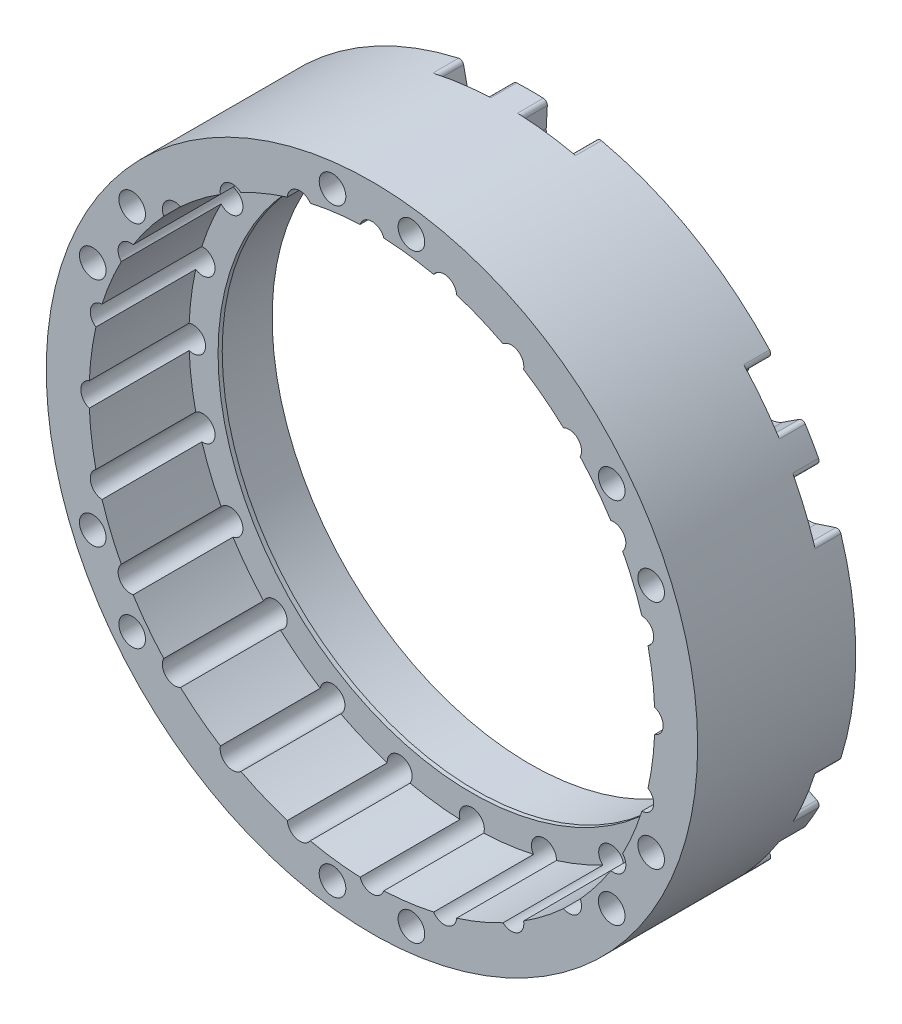
SolidWorks part; units mm, degrees
material "ABS"
ref_plane "Front Plane" through (0, 0, 0) normal (0, 0, 1) x (1, 0, 0)
ref_plane "Top Plane" through (0, 0, 0) normal (0, 1, 0) x (1, 0, 0)
ref_plane "Right Plane" through (0, 0, 0) normal (1, 0, 0) x (0, 0, -1)
sketch "CYC Master Sketch" plane through (0, 0, 0) normal (0, 0, 1) x (1, 0, 0)
  circle A0 centre (0, 0) radius 39.15
  circle A2 centre (0, 0) radius 33.5 construction
  circle A3 centre (-33.5, 0) radius 1.5
  circle A4 centre (-32.3585, 8.6704) radius 1.5
  circle A5 centre (-29.0119, 16.75) radius 1.5
  circle A6 centre (-23.6881, 23.6881) radius 1.5
  circle A7 centre (-16.75, 29.0119) radius 1.5
  circle A8 centre (-8.6704, 32.3585) radius 1.5
  circle A9 centre (0, 33.5) radius 1.5
  circle A10 centre (8.6704, 32.3585) radius 1.5
  circle A11 centre (16.75, 29.0119) radius 1.5
  circle A12 centre (23.6881, 23.6881) radius 1.5
  circle A13 centre (29.0119, 16.75) radius 1.5
  circle A14 centre (32.3585, 8.6704) radius 1.5
  circle A15 centre (33.5, 0) radius 1.5
  circle A16 centre (32.3585, -8.6704) radius 1.5
  circle A17 centre (29.0119, -16.75) radius 1.5
  circle A18 centre (23.6881, -23.6881) radius 1.5
  circle A19 centre (16.75, -29.0119) radius 1.5
  circle A20 centre (8.6704, -32.3585) radius 1.5
  circle A21 centre (0, -33.5) radius 1.5
  circle A22 centre (-8.6704, -32.3585) radius 1.5
  circle A23 centre (0, 0) radius 34
  circle A24 centre (-16.75, -29.0119) radius 1.5
  circle A25 centre (-23.6881, -23.6881) radius 1.5
  circle A26 centre (-29.0119, -16.75) radius 1.5
  circle A27 centre (-32.3585, -8.6704) radius 1.5
  circle A28 centre (0, 0) radius 31 construction
  circle A29 centre (0, 0) radius 25 construction
  circle A30 centre (0, 0) radius 36.325 construction
  circle A31 centre (4.7414, -36.0142) radius 1.6
  circle A32 centre (-4.7414, -36.0142) radius 1.6
  circle A33 centre (-28.8186, -22.1133) radius 1.6
  circle A34 centre (-33.5599, -13.901) radius 1.6
  circle A35 centre (-33.5599, 13.901) radius 1.6
  circle A36 centre (-28.8186, 22.1133) radius 1.6
  circle A37 centre (-4.7414, 36.0142) radius 1.6
  circle A38 centre (4.7414, 36.0142) radius 1.6
  circle A39 centre (28.8186, 22.1133) radius 1.6
  circle A40 centre (33.5599, 13.901) radius 1.6
  circle A41 centre (33.5599, -13.901) radius 1.6
  circle A42 centre (28.8186, -22.1133) radius 1.6
  point P47 (0, 0)
  point P72 (0, 0)
extrude "Gearbox Wall" add sketch "CYC Master Sketch" along normal blind 19 contours A0 A23 A13 A14 A15 A16 A17 A18 A19 A20 A21 A22 A3 A4 A5 A6 A7 A8 A9 A10 A11 A12 region at (-38.0427, 0, 0)
extrude "Gearbox Bottom" add sketch "CYC Master Sketch<3>" along normal blind 7 contours A21 A23 | A23 A20 | A20 A23 | A23 A19 | A19 A23 | A23 A18 | A18 A23 | A23 A17 | A17 A23 | A23 A16 | A16 A23 | A23 A15 | A15 A23 | A23 A14 | A14 A23 | A23 A13 | A13 A23 | A23 A12 | A12 A23 | A23 A11 | A11 A23 | A23 A10 | A10 A23 | A23 A9 | A9 A23 | A23 A8 | A8 A23 | A23 A7 | A7 A23 | A23 A6 | A6 A23 | A23 A5 | A5 A23 | A23 A4 | A4 A23 | A23 A3 | A3 A23 | A23 A22 | A22 A23 | A13 A23 A12 A11 A10 A9 A8 A7 A6 A5 A4 A3 A22 A21 A20 A19 A18 A17 A16 A15 A14 | A24 | A25 | A26 | A27 | A21 region at (-33.1184, 0, 0) region at (0, 0, 0) region at (-34.4085, 0, 0) region at (-31.99, 8.5717, 0) region at (-33.2361, 8.9056, 0) region at (-28.6814, 16.5592, 0) region at (-29.7987, 17.2043, 0) region at (-23.4183, 23.4183, 0) region at (-24.3305, 24.3305, 0) region at (-16.5592, 28.6814, 0) region at (-17.2043, 29.7987, 0) region at (-8.5717, 31.99, 0) region at (-8.9056, 33.2361, 0) region at (-8.9056, -33.2361, 0) region at (-8.5717, -31.99, 0) region at (0, 33.1184, 0) region at (0, 34.4085, 0) region at (0, -33.1184, 0) region at (8.5717, 31.99, 0) region at (8.9056, 33.2361, 0) region at (8.9056, -33.2361, 0) region at (8.5717, -31.99, 0) region at (16.5592, 28.6814, 0) region at (17.2043, 29.7987, 0) region at (17.2043, -29.7987, 0) region at (16.5592, -28.6814, 0) region at (23.4183, 23.4183, 0) region at (24.3305, 24.3305, 0) region at (24.3305, -24.3305, 0) region at (23.4183, -23.4183, 0) region at (28.6814, 16.5592, 0) region at (29.7987, 17.2043, 0) region at (29.7987, -17.2043, 0) region at (28.6814, -16.5592, 0) region at (31.99, 8.5717, 0) region at (33.2361, 8.9056, 0) region at (33.2361, -8.9056, 0) region at (31.99, -8.5717, 0) region at (33.1184, 0, 0) region at (34.4085, 0, 0)
sketch "CYC Master Sketch<3>" plane through (0, 0, 0) normal (0, 0, 1) x (1, 0, 0) same geometry as "CYC Master Sketch"
extrude "Pin Cut" cut sketch "CYC Master Sketch<2>" against normal blind 4 from surface contours A23 A7 | A7 A23 | A23 A6 | A6 A23 | A23 A5 | A5 A23 | A23 A4 | A4 A23 | A23 A3 | A3 A23 | A23 A22 | A22 A23 | A23 A21 | A21 A23 | A23 A20 | A20 A23 | A23 A19 | A19 A23 | A23 A18 | A18 A23 | A23 A17 | A17 A23 | A16 A23 | A23 A16 | A15 A23 | A23 A15 | A23 A14 | A14 A23 | A23 A13 | A13 A23 | A23 A12 | A12 A23 | A23 A11 | A11 A23 | A10 A23 | A23 A9 | A9 A23 | A23 A8 | A8 A23 | A23 A10 | A23 A24 | A23 A24 | A23 A25 | A23 A25 | A23 A26 | A23 A26 | A23 A27 | A23 A27 region at (-33.1184, 0, 0) region at (-34.4085, 0, 0) region at (-31.99, 8.5717, 0) region at (-33.2361, 8.9056, 0) region at (-31.99, -8.5717, 0) region at (-33.2361, -8.9056, 0) region at (-28.6814, 16.5592, 0) region at (-29.7987, 17.2043, 0) region at (-28.6814, -16.5592, 0) region at (-29.7987, -17.2043, 0) region at (-23.4183, 23.4183, 0) region at (-24.3305, 24.3305, 0) region at (-23.4183, -23.4183, 0) region at (-24.3305, -24.3305, 0) region at (-16.5592, 28.6814, 0) region at (-17.2043, 29.7987, 0) region at (-16.5592, -28.6814, 0) region at (-17.2043, -29.7987, 0) region at (-8.5717, 31.99, 0) region at (-8.9056, 33.2361, 0) region at (-8.9056, -33.2361, 0) region at (-8.5717, -31.99, 0) region at (0, 33.1184, 0) region at (0, 34.4085, 0) region at (0, -34.4085, 0) region at (0, -33.1184, 0) region at (8.5717, 31.99, 0) region at (8.9056, 33.2361, 0) region at (8.9056, -33.2361, 0) region at (8.5717, -31.99, 0) region at (16.5592, 28.6814, 0) region at (17.2043, 29.7987, 0) region at (17.2043, -29.7987, 0) region at (16.5592, -28.6814, 0) region at (23.4183, 23.4183, 0) region at (24.3305, 24.3305, 0) region at (24.3305, -24.3305, 0) region at (23.4183, -23.4183, 0) region at (28.6814, 16.5592, 0) region at (29.7987, 17.2043, 0) region at (29.7987, -17.2043, 0) region at (28.6814, -16.5592, 0) region at (31.99, 8.5717, 0) region at (33.2361, 8.9056, 0) region at (33.2361, -8.9056, 0) region at (31.99, -8.5717, 0) region at (33.1184, 0, 0) region at (34.4085, 0, 0) starting at face at (0, 0, 7)
sketch "CYC Master Sketch<2>" plane through (0, 0, 0) normal (0, 0, 1) x (1, 0, 0) same geometry as "CYC Master Sketch"
sketch "CYC Master" plane through (0, 0, 7) normal (0, 0, 1) x (1, 0, 0)
  circle A0 centre (0, 0) radius 39.15
  circle A2 centre (0, 0) radius 33.5 construction
  circle A3 centre (-33.5, 0) radius 1.5
  circle A4 centre (-32.3585, 8.6704) radius 1.5
  circle A5 centre (-29.0119, 16.75) radius 1.5
  circle A6 centre (-23.6881, 23.6881) radius 1.5
  circle A7 centre (-16.75, 29.0119) radius 1.5
  circle A8 centre (-8.6704, 32.3585) radius 1.5
  circle A9 centre (0, 33.5) radius 1.5
  circle A10 centre (8.6704, 32.3585) radius 1.5
  circle A11 centre (16.75, 29.0119) radius 1.5
  circle A12 centre (23.6881, 23.6881) radius 1.5
  circle A13 centre (29.0119, 16.75) radius 1.5
  circle A14 centre (32.3585, 8.6704) radius 1.5
  circle A15 centre (33.5, 0) radius 1.5
  circle A16 centre (32.3585, -8.6704) radius 1.5
  circle A17 centre (29.0119, -16.75) radius 1.5
  circle A18 centre (23.6881, -23.6881) radius 1.5
  circle A19 centre (16.75, -29.0119) radius 1.5
  circle A20 centre (8.6704, -32.3585) radius 1.5
  circle A21 centre (0, -33.5) radius 1.5
  circle A22 centre (-8.6704, -32.3585) radius 1.5
  circle A23 centre (0, 0) radius 34
  circle A24 centre (-16.75, -29.0119) radius 1.5
  circle A25 centre (-23.6881, -23.6881) radius 1.5
  circle A26 centre (-29.0119, -16.75) radius 1.5
  circle A27 centre (-32.3585, -8.6704) radius 1.5
  circle A28 centre (0, 0) radius 31 construction
  circle A29 centre (0, 0) radius 25 construction
  circle A30 centre (0, 0) radius 36.325 construction
  circle A31 centre (4.7414, -36.0142) radius 1.6
  circle A32 centre (-4.7414, -36.0142) radius 1.6
  circle A33 centre (-28.8186, -22.1133) radius 1.6
  circle A34 centre (-33.5599, -13.901) radius 1.6
  circle A35 centre (-33.5599, 13.901) radius 1.6
  circle A36 centre (-28.8186, 22.1133) radius 1.6
  circle A37 centre (-4.7414, 36.0142) radius 1.6
  circle A38 centre (4.7414, 36.0142) radius 1.6
  circle A39 centre (28.8186, 22.1133) radius 1.6
  circle A40 centre (33.5599, 13.901) radius 1.6
  circle A41 centre (33.5599, -13.901) radius 1.6
  circle A42 centre (28.8186, -22.1133) radius 1.6
  point P47 (0, 0)
  point P72 (0, 0)
sketch "Sketch2" plane through (0, 0, 7) normal (0, 0, 1) x (1, 0, 0)
  circle A0 centre (0, 0) radius 31
  circle A1 centre (0, 0) radius 31 construction
extrude "Housing Bearing Cut" cut sketch "Sketch2" against normal through all
sketch "Sketch3" plane through (0, 0, 7) normal (0, 0, 1) x (1, 0, 0)
  circle A0 centre (0, 0) radius 31
  circle A1 centre (0, 0) radius 30.5
  circle A2 centre (0, 0) radius 31 construction
  dimension "D1" = 61
  dimension "Housing Bearing Outer (Driven)" = 62
extrude "Housing Bearing Retainer" add sketch "Sketch3" against normal blind 0.5
sketch "Sketch5" plane through (0, 0, 0) normal (0, 0, -1) x (-1, 0, 0)
  line L0 (0, 0) -> (32.2922, 16.3975) construction
  line L1 (0, 0) -> (34.4288, 11.2392) construction
  line L2 (34.4288, 11.2392) -> (37.2171, 12.1494)
  line L3 (32.2922, 16.3975) -> (34.9074, 17.7255)
  line L4 (0, 0) -> (33.9049, 19.575) construction
  line L5 (26.9479, 24.1967) -> (29.1303, 26.1562)
  line L6 (30.3468, 19.7671) -> (32.8045, 21.368)
  line L7 (34.4288, -11.2392) -> (37.2171, -12.1494)
  line L8 (32.2922, -16.3975) -> (34.9074, -17.7255)
  line L9 (26.9479, -24.1967) -> (29.1303, -26.1562)
  line L10 (30.3468, -19.7671) -> (32.8045, -21.368)
  line L11 (7.481, -35.4359) -> (8.0868, -38.3057)
  line L12 (1.9454, -36.1646) -> (2.103, -39.0935)
  line L13 (-7.481, -35.4359) -> (-8.0868, -38.3057)
  line L14 (-1.9454, -36.1646) -> (-2.103, -39.0935)
  line L15 (-26.9479, -24.1967) -> (-29.1303, -26.1562)
  line L16 (-30.3468, -19.7671) -> (-32.8045, -21.368)
  line L17 (-34.4288, -11.2392) -> (-37.2171, -12.1494)
  line L18 (-32.2922, -16.3975) -> (-34.9074, -17.7255)
  line L19 (-34.4288, 11.2392) -> (-37.2171, 12.1494)
  line L20 (-32.2922, 16.3975) -> (-34.9074, 17.7255)
  line L21 (-26.9479, 24.1967) -> (-29.1303, 26.1562)
  line L22 (-30.3468, 19.7671) -> (-32.8045, 21.368)
  line L23 (-7.481, 35.4359) -> (-8.0868, 38.3057)
  line L24 (-1.9454, 36.1646) -> (-2.103, 39.0935)
  line L25 (7.481, 35.4359) -> (8.0868, 38.3057)
  line L26 (1.9454, 36.1646) -> (2.103, 39.0935)
  arc A0 (32.2922, 16.3975) -> (34.4288, 11.2392) centre (33.5599, 13.901) ccw
  arc A1 (-32.8045, -21.368) -> (-29.1303, -26.1562) centre (0, 0) ccw
  circle A2 centre (0, 0) radius 39.15 construction
  arc A3 (34.9074, 17.7255) -> (37.2171, 12.1494) centre (0, 0) cw
  arc A4 (32.8045, 21.368) -> (29.1303, 26.1562) centre (0, 0) ccw
  arc A5 (30.3468, 19.7671) -> (26.9479, 24.1967) centre (28.8186, 22.1133) cw
  arc A6 (34.9074, -17.7255) -> (37.2171, -12.1494) centre (0, 0) ccw
  arc A7 (32.2922, -16.3975) -> (34.4288, -11.2392) centre (33.5599, -13.901) cw
  arc A8 (32.8045, -21.368) -> (29.1303, -26.1562) centre (0, 0) cw
  arc A9 (30.3468, -19.7671) -> (26.9479, -24.1967) centre (28.8186, -22.1133) ccw
  arc A10 (2.103, -39.0935) -> (8.0868, -38.3057) centre (0, 0) ccw
  arc A11 (1.9454, -36.1646) -> (7.481, -35.4359) centre (4.7414, -36.0142) cw
  arc A12 (-2.103, -39.0935) -> (-8.0868, -38.3057) centre (0, 0) cw
  arc A13 (-1.9454, -36.1646) -> (-7.481, -35.4359) centre (-4.7414, -36.0142) ccw
  arc A14 (-30.3468, -19.7671) -> (-26.9479, -24.1967) centre (-28.8186, -22.1133) cw
  arc A15 (-34.9074, -17.7255) -> (-37.2171, -12.1494) centre (0, 0) cw
  arc A16 (-32.2922, -16.3975) -> (-34.4288, -11.2392) centre (-33.5599, -13.901) ccw
  arc A17 (-34.9074, 17.7255) -> (-37.2171, 12.1494) centre (0, 0) ccw
  arc A18 (-32.2922, 16.3975) -> (-34.4288, 11.2392) centre (-33.5599, 13.901) cw
  arc A19 (-32.8045, 21.368) -> (-29.1303, 26.1562) centre (0, 0) cw
  arc A20 (-30.3468, 19.7671) -> (-26.9479, 24.1967) centre (-28.8186, 22.1133) ccw
  arc A21 (-2.103, 39.0935) -> (-8.0868, 38.3057) centre (0, 0) ccw
  arc A22 (-1.9454, 36.1646) -> (-7.481, 35.4359) centre (-4.7414, 36.0142) cw
  arc A23 (2.103, 39.0935) -> (8.0868, 38.3057) centre (0, 0) cw
  arc A24 (1.9454, 36.1646) -> (7.481, 35.4359) centre (4.7414, 36.0142) ccw
  point P39 (0, 0)
  dimension "D1" = 5.6
  dimension "D3" = 6
  dimension "D2" = 7.5
extrude "M3 Socket Head Cutout" cut sketch "Sketch5" against normal blind 3.1
fillet "Fillet1" radius 0.5 24 edges at (-8.0868, -38.3057, 1.55) (-2.103, -39.0935, 1.55) (2.103, -39.0935, 1.55) (8.0868, -38.3057, 1.55) (-29.1303, -26.1562, 1.55) (-32.8045, -21.368, 1.55) (-37.2171, -12.1494, 1.55) (-34.9074, -17.7255, 1.55) (-29.1303, 26.1562, 1.55) (-32.8045, 21.368, 1.55) (-34.9074, 17.7255, 1.55) (-37.2171, 12.1494, 1.55) (-8.0868, 38.3057, 1.55) (-2.103, 39.0935, 1.55) (8.0868, 38.3057, 1.55) (2.103, 39.0935, 1.55) (29.1303, 26.1562, 1.55) (32.8045, 21.368, 1.55) (34.9074, 17.7255, 1.55) (37.2171, 12.1494, 1.55) (37.2171, -12.1494, 1.55) (34.9074, -17.7255, 1.55) (32.8045, -21.368, 1.55) (29.1303, -26.1562, 1.55)
equation "\"D1@Sketch3\" = \"Housing Bearing Outer (Driven)@Sketch3\" - 1"
